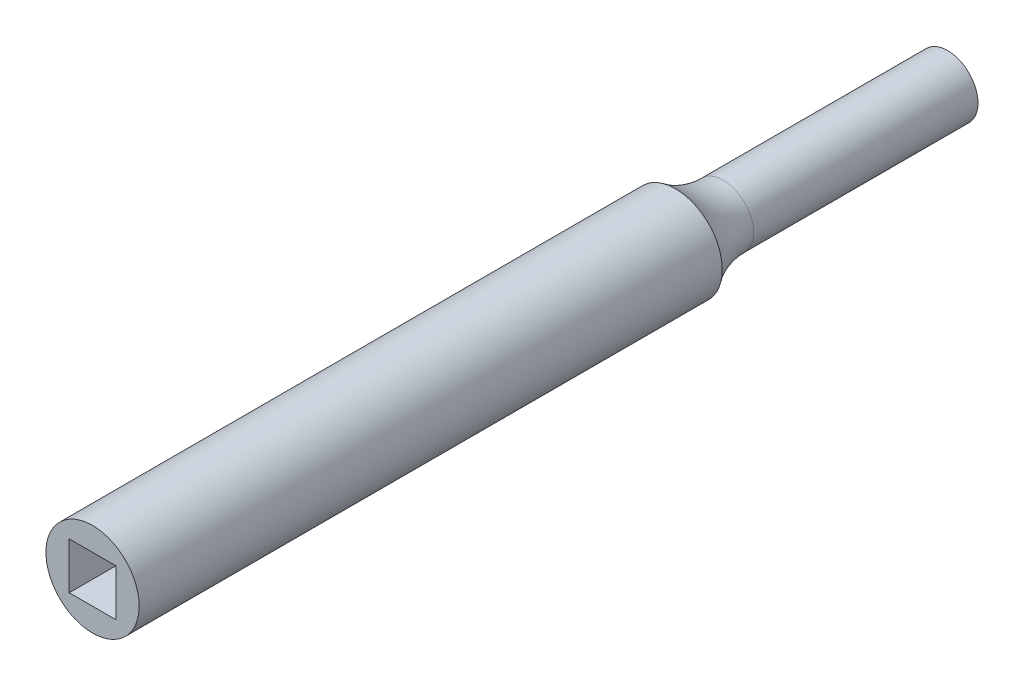
SolidWorks part; units mm, degrees
ref_plane "Front Plane" through (0, 0, 0) normal (0, 0, 1) x (1, 0, 0)
ref_plane "Top Plane" through (0, 0, 0) normal (0, 1, 0) x (1, 0, 0)
ref_plane "Right Plane" through (0, 0, 0) normal (1, 0, 0) x (0, 0, -1)
sketch "Sketch5" plane through (0, 0, 0) normal (0, 0, 1) x (1, 0, 0)
  circle A0 centre (0, 0) radius 3.9
  dimension "D1" = 7.8
extrude "Boss-Extrude4" add sketch "Sketch5" along normal blind 35
sketch "Sketch6" plane through (0, 0, 35) normal (0, 0, 1) x (1, 0, 0)
  circle A0 centre (0, 0) radius 6
  dimension "D1" = 12
extrude "Boss-Extrude5" add sketch "Sketch6" along normal blind 75
fillet "Fillet1" radius 10 1 edges at (3.9, 0, 35)
sketch "Sketch7" plane through (0, 0, 110) normal (0, 0, 1) x (1, 0, 0)
  line L1 (3, 3) -> (-3, 3)
  line L2 (3, 3) -> (3, -3)
  line L3 (3, -3) -> (-3, -3)
  line L4 (-3, 3) -> (-3, -3)
  circle A0 centre (0, 0) radius 6 construction
  dimension "D1" = 6
  dimension "D2" = 6
  dimension "D3" = 3
  dimension "D4" = 3
extrude "Cut-Extrude1" cut sketch "Sketch7" against normal blind 20
